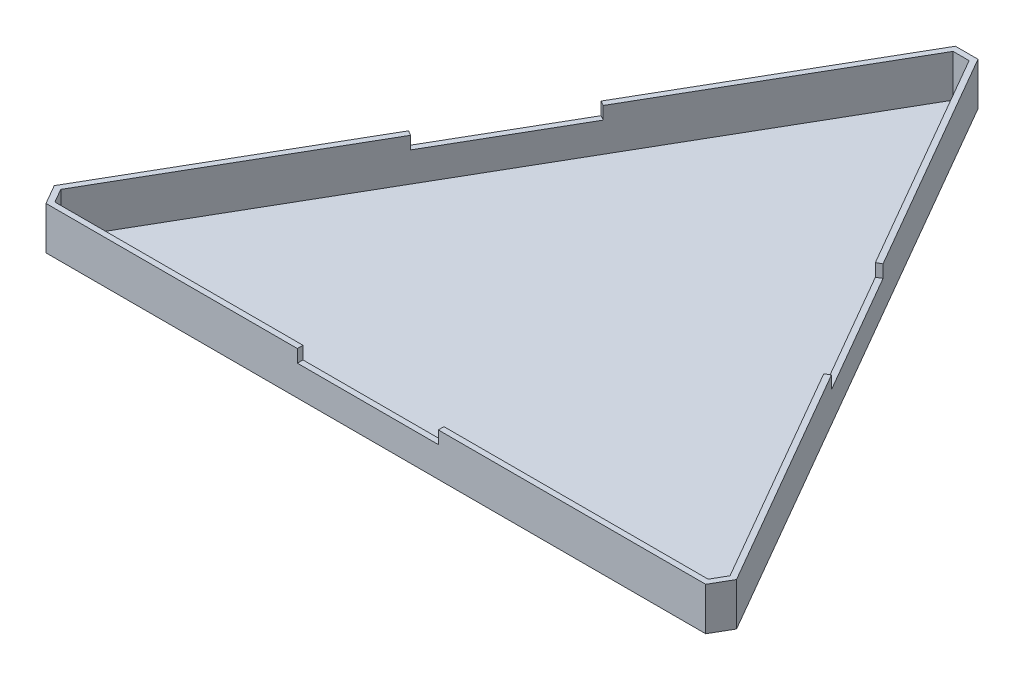
SolidWorks part; units mm, degrees
ref_plane "Front Plane" through (0, 0, 0) normal (0, 0, 1) x (1, 0, 0)
ref_plane "Top Plane" through (0, 0, 0) normal (0, 1, 0) x (1, 0, 0)
ref_plane "Right Plane" through (0, 0, 0) normal (1, 0, 0) x (0, 0, -1)
sketch "Sketch1" plane through (0, 0, 0) normal (0, 1, 0) x (1, 0, 0)
  line L0 (351.2729, 67.6655) -> (468.273, -134.9846)
  line L1 (231.428, -139.9124) -> (463.1186, -139.9124)
  line L3 (468.273, -134.9846) -> (464.2732, -141.9124)
  line L4 (230.2733, -141.9124) -> (464.2732, -141.9124)
  line L5 (230.2733, -141.9124) -> (226.2727, -134.9842)
  line L6 (226.2727, -134.9842) -> (343.2728, 67.6655)
  line L20 (343.2728, 67.6655) -> (351.2729, 67.6655)
  line L26 (231.428, -139.9124) -> (228.582, -134.9842)
  line L27 (228.582, -134.9842) -> (344.4274, 65.6656)
  line L28 (344.4274, 65.6656) -> (350.1183, 65.6656)
  line L29 (350.1183, 65.6656) -> (465.9637, -134.9846)
  line L30 (465.9637, -134.9846) -> (463.1186, -139.9124)
extrude "Boss-Extrude6" add sketch "Sketch1" along normal blind 0.2 contours L0 L3 L4 L5 L6 L20
extrude "Boss-Extrude8" add sketch "Sketch1<7>" along normal blind 15.2
sketch "Sketch1<7>" plane through (0, 0, 0) normal (0, 1, 0) x (1, 0, 0) same geometry as "Sketch1"
sketch "Sketch2" plane through (0, 0, 141.9124) normal (0, 0, 1) x (1, 0, 0)
  line L1 (319.4274, 19.7) -> (369.4274, 19.7)
  line L2 (319.4274, 19.7) -> (319.4274, 10.7)
  line L3 (319.4274, 10.7) -> (369.4274, 10.7)
  line L4 (369.4274, 19.7) -> (369.4274, 10.7)
  line L5 (319.4274, 19.7) -> (369.4274, 10.7) construction
  line L6 (319.4274, 10.7) -> (369.4274, 19.7) construction
  point P0 (344.4274, 15.2)
  dimension "D1" = 9
  dimension "D2" = 50
extrude "Cut-Extrude1" cut sketch "Sketch2" against normal blind 2
sketch "Sketch3" plane through (292.7547, 0, -169.022) normal (0.866, 0, -0.5) x (-0.5, 0, -0.866)
  line L0 (-351.0366, 15.2) -> (-117.0364, 15.2) construction
  line L1 (-259.0365, 19.7) -> (-209.0365, 19.7)
  line L2 (-259.0365, 19.7) -> (-259.0365, 10.7)
  line L3 (-259.0365, 10.7) -> (-209.0365, 10.7)
  line L4 (-209.0365, 19.7) -> (-209.0365, 10.7)
  line L5 (-259.0365, 19.7) -> (-209.0365, 10.7) construction
  line L6 (-259.0365, 10.7) -> (-209.0365, 19.7) construction
  point P0 (-234.0365, 15.2)
  dimension "D1" = 9
  dimension "D2" = 50
extrude "Cut-Extrude2" cut sketch "Sketch3" against normal blind 2
sketch "Sketch4" plane through (228.1543, 0, 131.7252) normal (-0.866, 0, -0.5) x (-0.5, 0, 0.866)
  line L0 (-230.2366, 15.2) -> (3.7633, 15.2) construction
  line L1 (-138.2367, 19.7) -> (-88.2367, 19.7)
  line L2 (-138.2367, 19.7) -> (-138.2367, 10.7)
  line L3 (-138.2367, 10.7) -> (-88.2367, 10.7)
  line L4 (-88.2367, 19.7) -> (-88.2367, 10.7)
  line L5 (-138.2367, 19.7) -> (-88.2367, 10.7) construction
  line L6 (-138.2367, 10.7) -> (-88.2367, 19.7) construction
  point P0 (-113.2367, 15.2)
  dimension "D1" = 50
  dimension "D2" = 9
extrude "Cut-Extrude3" cut sketch "Sketch4" against normal blind 2
